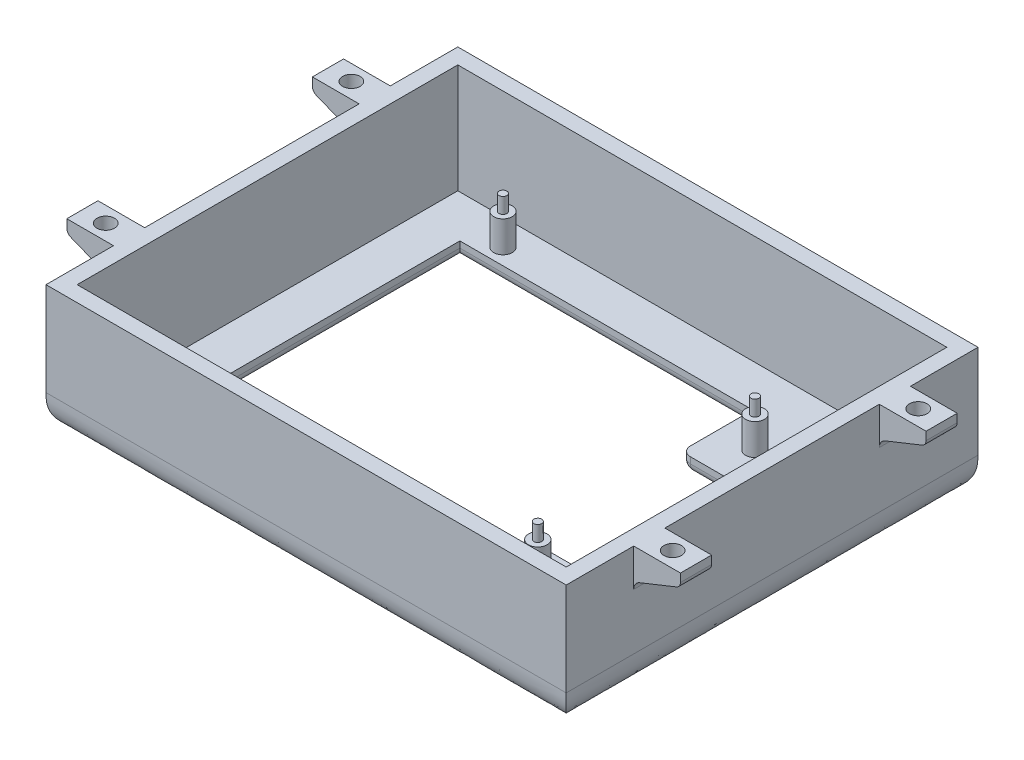
SolidWorks part; units mm, degrees
ref_plane "Ebene vorne" through (0, 0, 0) normal (0, 0, 1) x (1, 0, 0)
ref_plane "Ebene oben" through (0, 0, 0) normal (0, 1, 0) x (1, 0, 0)
ref_plane "Ebene rechts" through (0, 0, 0) normal (1, 0, 0) x (0, 0, -1)
sketch "Skizze1" plane through (0, 0, 0) normal (0, 1, 0) x (1, 0, 0)
  line L0 (-57.4441, 0) -> (108.4227, 0) construction
  line L1 (-83.5, 66.1) -> (83.5, 66.1)
  line L2 (-83.5, 66.1) -> (-83.5, -66.1)
  line L3 (-83.5, -66.1) -> (83.5, -66.1)
  line L4 (83.5, 66.1) -> (83.5, -66.1)
  line L5 (0, 55.397) -> (0, -92.4842) construction
  dimension "D1" = 167
  dimension "D2" = 132.2
extrude "Aufsatz-Linear austragen1" add sketch "Skizze1" along normal blind 80
sketch "Skizze2" plane through (0, 80, 0) normal (0, 1, 0) x (1, 0, 0)
  line L0 (0, 52.0751) -> (0, -71.1014) construction
  line L1 (-78.5, 61.1) -> (78.5, 61.1)
  line L2 (-78.5, 61.1) -> (-78.5, -61.1)
  line L3 (-78.5, -61.1) -> (78.5, -61.1)
  line L4 (78.5, 61.1) -> (78.5, -61.1)
  line L5 (-41.5118, 0) -> (56.2139, 0) construction
  line L6 (-83.5, 66.1) -> (-83.5, -66.1) construction
  line L7 (83.5, 66.1) -> (-83.5, 66.1) construction
  dimension "D1" = 5
  dimension "D2" = 5
extrude "Schnitt-Linear austragen1" cut sketch "Skizze2" against normal blind 75
sketch "Platine" plane through (0, 5, 0) normal (0, 1, 0) x (1, 0, 0)
  line L0 (0, 25.5089) -> (0, -13.445) construction
  line L1 (-17.8492, 0) -> (15.1436, 0) construction
  line L2 (33.515, 54.5281) -> (33.515, -95.4394) construction
  line L3 (58.415, 73.5618) -> (58.415, -76.4057) construction
  line L6 (24.1073, 11.505) -> (87.4465, 11.505) construction
  line L7 (33.8429, -13.445) -> (97.1821, -13.445) construction
  line L8 (-58.415, 56.095) -> (33.515, 56.095)
  line L9 (33.515, 56.095) -> (58.415, 11.505)
  line L10 (58.415, 11.505) -> (58.415, -13.445)
  line L11 (58.415, -13.445) -> (33.515, -56.095)
  line L12 (33.515, -56.095) -> (-58.415, -56.095)
  line L13 (-58.415, -56.095) -> (-58.415, 56.095)
  dimension "D1" = 112.19
  dimension "D2" = 91.93
  dimension "D3" = 24.9
  dimension "D4" = 44.59
  dimension "D5" = 24.95
sketch "Skizze4" plane through (0, 5, 0) normal (0, 1, 0) x (1, 0, 0)
  line L1 (-58.415, -56.095) -> (-58.415, 56.095) construction
  line L2 (-58.415, 56.095) -> (33.515, 56.095) construction
  line L3 (33.515, -56.095) -> (-58.415, -56.095) construction
  line L4 (58.415, 11.505) -> (58.415, -13.445) construction
  circle A0 centre (-55.5494, 52.655) radius 2.985
  circle A1 centre (-55.5494, -53.3587) radius 3
  circle A2 centre (41.2513, -32.9612) radius 3
  circle A3 centre (41.2513, 36.7522) radius 3
  dimension "D9" = 5.97
  dimension "D10" = 6
  dimension "D11" = 6
  dimension "D12" = 6
  dimension "D1" = 2.8656
  dimension "D2" = 3.44
  dimension "D3" = 2.8656
  dimension "D4" = 2.7363
  dimension "D5" = 19.3428
  dimension "D6" = 17.1638
  dimension "D7" = 23.1337
  dimension "D8" = 17.1638
extrude "Aufsatz-Linear austragen2" add sketch "Skizze4" along normal blind 10
sketch "Skizze5" plane through (0, 15, 0) normal (0, 1, 0) x (1, 0, 0)
  circle A0 centre (-55.5494, 52.655) radius 1.25
  circle A1 centre (41.2513, 36.7522) radius 1.25
  circle A2 centre (41.2513, -32.9612) radius 1.25
  circle A3 centre (-55.5494, -53.3587) radius 1.25
  dimension "D1" = 2.5
  dimension "D2" = 2.5
  dimension "D3" = 2.5
  dimension "D4" = 2.5
extrude "Aufsatz-Linear austragen3" add sketch "Skizze5" along normal blind 5
sketch "Skizze6" plane through (0, 0, 0) normal (0, -1, 0) x (1, 0, 0)
  line L0 (29.767, 24.5) -> (29.767, 47.5)
  line L1 (-64.233, 47.5) -> (29.767, 47.5)
  line L2 (-64.233, 47.5) -> (-64.233, -47.5)
  line L3 (-64.233, -47.5) -> (29.767, -47.5)
  line L5 (0, 0) -> (0, 41.5649) construction
  line L6 (0, 0) -> (-36.8563, 0) construction
  line L7 (29.767, 24.5) -> (58.415, 24.5)
  line L8 (58.415, -73.5618) -> (58.415, 76.4057) construction
  line L9 (58.415, 24.5) -> (58.415, -24.5)
  line L10 (58.415, -24.5) -> (29.767, -24.5)
  line L12 (29.767, -24.5) -> (29.767, -47.5)
  dimension "D1" = 95
  dimension "D2" = 94
  dimension "D3" = 23
  dimension "D4" = 94
extrude "Schnitt-Linear austragen2" cut sketch "Skizze6" against normal blind 5
ref_plane "Ebene1" through (0, 74, 0) normal (0, 1, 0) x (1, 0, 0)
fillet "Verrundung4" radius 10 4 edges at (-83.5, 0, 0) (0, 0, -66.1) (0, 0, 66.1) (83.5, 0, 0) curvature continuous yes
fillet "Verrundung5" radius 3 8 edges at (29.767, 0, 36) (44.091, 0, 24.5) (58.415, 0, 0) (44.091, 0, -24.5) (29.767, 0, -36) (-17.233, 0, -47.5) (-64.233, 0, 0) (-17.233, 0, 47.5)
fillet "Verrundung6" radius 3 4 edges at (30.6457, 0.8787, -25.3787) (30.6457, 0.8787, 25.3787) (29.767, 4, -24.5) (29.767, 4, 24.5)
sketch "Skizze14" plane through (0, 80, 0) normal (0, 1, 0) x (1, 0, 0)
  line L1 (-99.5816, 68.6273) -> (100.6844, 68.6273)
  line L2 (-99.5816, 68.6273) -> (-99.5816, -70.1033)
  line L3 (-99.5816, -70.1033) -> (100.6844, -70.1033)
  line L4 (100.6844, 68.6273) -> (100.6844, -70.1033)
extrude "Schnitt-Linear austragen11" cut sketch "Skizze14" against normal blind 40
ref_plane "EbeneBefestigung" through (0, 40, 0) normal (0, -1, 0) x (-1, 0, 0)
sketch "Skizze17" plane through (0, 40, 0) normal (0, -1, 0) x (-1, 0, 0)
  line L0 (83.5, 66.1) -> (83.5, -66.1) construction
  line L1 (83.5, 44.4255) -> (98.5, 44.4255)
  line L2 (83.5, 44.4255) -> (83.5, 34.4255)
  line L3 (83.5, 34.4255) -> (98.5, 34.4255)
  line L4 (98.5, 44.4255) -> (98.5, 34.4255)
  line L5 (83.5, 0) -> (-83.5, 0) construction
  line L6 (-83.5, -66.1) -> (-83.5, 66.1) construction
  line L7 (98.5, -44.4255) -> (98.5, -34.4255)
  line L8 (83.5, -34.4255) -> (98.5, -34.4255)
  line L9 (83.5, -44.4255) -> (83.5, -34.4255)
  line L10 (83.5, -44.4255) -> (98.5, -44.4255)
  line L11 (0, 66.1) -> (0, -66.1) construction
  line L12 (-83.5, 66.1) -> (83.5, 66.1) construction
  line L13 (83.5, -66.1) -> (-83.5, -66.1) construction
  line L14 (-83.5, -44.4255) -> (-98.5, -44.4255)
  line L15 (-83.5, -44.4255) -> (-83.5, -34.4255)
  line L16 (-83.5, -34.4255) -> (-98.5, -34.4255)
  line L17 (-98.5, -44.4255) -> (-98.5, -34.4255)
  line L18 (-98.5, 44.4255) -> (-98.5, 34.4255)
  line L19 (-83.5, 34.4255) -> (-98.5, 34.4255)
  line L20 (-83.5, 44.4255) -> (-83.5, 34.4255)
  line L21 (-83.5, 44.4255) -> (-98.5, 44.4255)
  line L22 (-98.5, 39.4255) -> (-83.5, 39.4255) construction
  line L23 (-91, 44.4255) -> (-91, 34.4255) construction
  circle A0 centre (-91, 39.4255) radius 2.8
  circle A1 centre (-91, -39.4255) radius 2.8
  circle A2 centre (91, -39.4255) radius 2.8
  circle A3 centre (91, 39.4255) radius 2.8
  point P35 (-91, 39.4255)
  dimension "D3" = 5.6
  dimension "D1" = 10
  dimension "D2" = 15
extrude "Aufsatz-Linear austragen4" add sketch "Skizze17" along normal blind 10
sketch "Skizze18" plane through (0, 0, 44.4255) normal (0, 0, 1) x (1, 0, 0)
  line L3 (-98.5, 36) -> (-83.5, 30)
  line L4 (-98.5, 30) -> (-98.5, 40) construction
  line L5 (-83.5, 30) -> (-98.5, 30)
  line L6 (-98.5, 30) -> (-98.5, 36)
  line L7 (-83.5, 40) -> (-98.5, 40) construction
  line L8 (0, 40) -> (0, 0) construction
  line L9 (-83.5, 40) -> (83.5, 40) construction
  line L10 (98.5, 30) -> (98.5, 36)
  line L11 (83.5, 30) -> (98.5, 30)
  line L12 (98.5, 36) -> (83.5, 30)
  dimension "D1" = 4
extrude "Schnitt-Linear austragen12" cut sketch "Skizze18" against normal through all
ref_plane "Ebene3" through (0, 35, 0) normal (0, 1, 0) x (1, 0, 0)
sketch "Skizze20" plane through (0, 35, 0) normal (0, 1, 0) x (1, 0, 0)
  line L0 (-83.5, 0) -> (83.5, 0) construction
  line L1 (-83.5, 34.4255) -> (-83.5, -34.4255) construction
  line L2 (83.5, -34.4255) -> (83.5, 34.4255) construction
  line L3 (0, 66.1) -> (0, -66.1) construction
  line L4 (83.5, 66.1) -> (-83.5, 66.1) construction
  line L5 (-83.5, -66.1) -> (83.5, -66.1) construction
  circle A0 centre (-91, 39.4255) radius 4.3
  circle A1 centre (-91, -39.4255) radius 4.3
  circle A2 centre (91, -39.4255) radius 4.3
  circle A3 centre (91, 39.4255) radius 4.3
  dimension "D1" = 8.6
extrude "Schnitt-Linear austragen13" cut sketch "Skizze20" against normal blind 10
fillet "Verrundung7" radius 3 4 edges at (83.5, 30, -39.4255) (83.5, 30, 39.4255) (-83.5, 30, 39.4255) (-83.5, 30, -39.4255)
fillet "Verrundung8" radius 2 4 edges at (-98.5, 36, 39.4255) (-98.5, 36, -39.4255) (98.5, 36, -39.4255) (98.5, 36, 39.4255)
